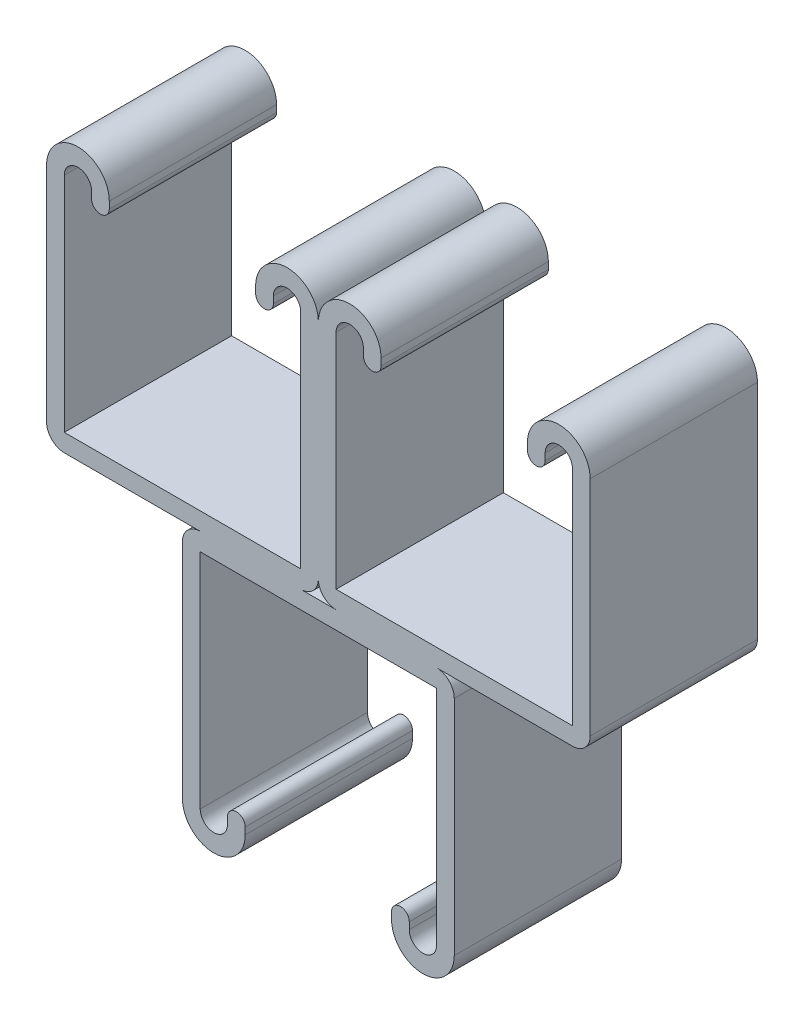
SolidWorks part; units mm, degrees
note: '?' marks a value the reader was unsure of.
ref_plane "Plane1" through (0, 0, 0) normal (0, 0, 1) x (1, 0, 0)
ref_plane "Plane2" through (0, 0, 0) normal (0, 1, 0) x (1, 0, 0)
ref_plane "Plane3" through (0, 0, 0) normal (1, 0, 0) x (0, 0, -1)
sketch "Sketch1" plane through (0, 0, 0) normal (0, 0, 1) x (1, 0, 0)
  line L0 (-30.9563, 36.5125) -> (-30.9562, 2.6924)
  line L1 (-28.2638, 0) -> (7.6264, 0)
  line L2 (10.3188, 2.6924) -> (10.3188, 36.5125)
  line L3 (0.7937, 36.5125) -> (0.7937, 35.4774)
  line L4 (-21.4312, 36.5125) -> (-21.4312, 35.4774)
  line L5 (-24.1236, 36.5125) -> (-24.1236, 35.4774)
  line L6 (-28.2639, 36.5125) -> (-28.2638, 2.6924)
  line L7 (-28.2638, 2.6924) -> (7.6264, 2.6924)
  line L8 (7.6264, 2.6924) -> (7.6264, 36.5125)
  line L9 (3.4862, 36.5125) -> (3.4862, 35.4774)
  line L10 (-25.4, 41.275) -> (25.4, 41.275) construction
  line L11 (-12.8524, 34.1313) -> (12.8524, 34.1313) construction
  arc A0 (10.3188, 36.5125) -> (0.7937, 36.5125) centre (5.5562, 36.5125) ccw
  arc A1 (-30.9563, 36.5125) -> (-21.4312, 36.5125) centre (-26.1937, 36.5125) cw
  arc A2 (-28.2638, 0) -> (-30.9562, 2.6924) centre (-28.2638, 2.6924) cw
  arc A3 (7.6264, 0) -> (10.3188, 2.6924) centre (7.6264, 2.6924) ccw
  arc A4 (-28.2639, 36.5125) -> (-24.1236, 36.5125) centre (-26.1937, 36.5125) cw
  arc A5 (7.6264, 36.5125) -> (3.4862, 36.5125) centre (5.5562, 36.5125) ccw
  arc A6 (0.7937, 35.4774) -> (3.4862, 35.4774) centre (2.1399, 35.4774) ccw
  arc A7 (-21.4312, 35.4774) -> (-24.1236, 35.4774) centre (-22.7774, 35.4774) cw
  dimension "D3" = 30.9562
  dimension "D6" = 9.525
  dimension "D7" = 22.225
  dimension "D9" = 7.1437
  dimension "D2" = 41.275
extrude "Base-Extrude" add sketch "Sketch1" along normal mid plane 25.4
ref_axis "Axis1" through (0, 0, -50) along (0, 0, 1)?
pattern_circular "CirPattern1" count 2 every 180 about axis through (0, 0, 0) along (0, 0, 1) of "Base-Extrude"
pattern_linear "LPattern1" count 2 spacing 41.275 along (1, 0, 0) of "Base-Extrude"
equation "\"D7@Sketch1\" = \"Width@Sketch1\" - 2 * \"D6@Sketch1\""
equation "\"D1@Sketch1\" = \"gauge@Sketch1\""
